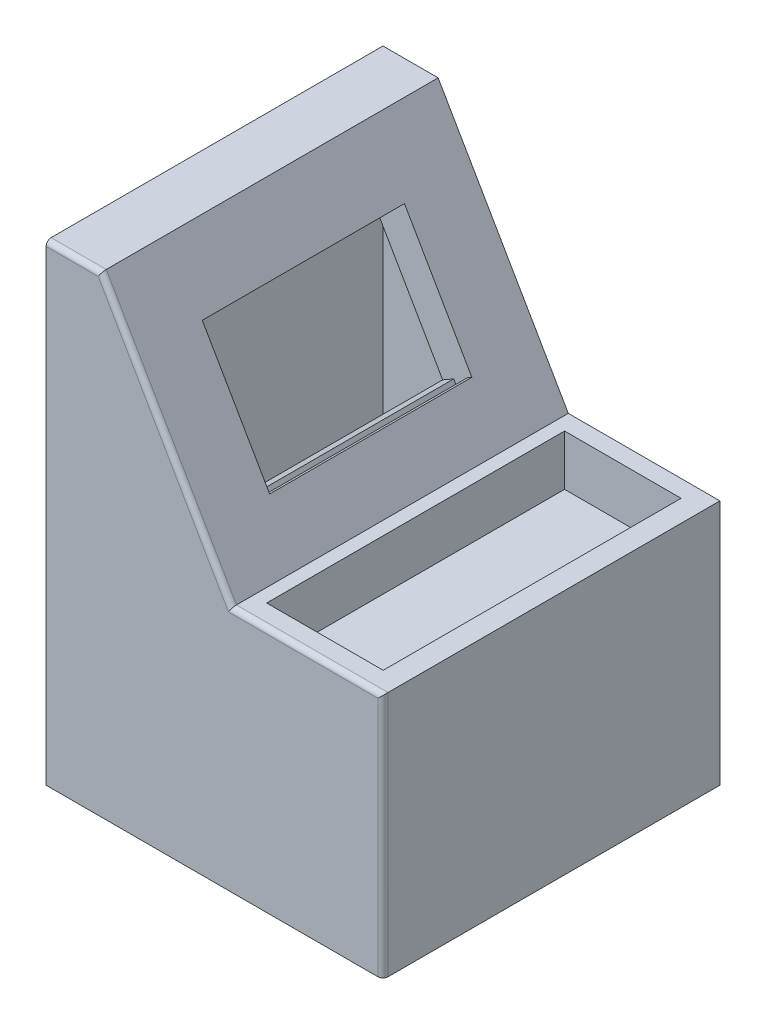
SolidWorks part; units mm, degrees
ref_plane "Front Plane" through (0, 0, 0) normal (0, 0, 1) x (1, 0, 0)
ref_plane "Top Plane" through (0, 0, 0) normal (0, 1, 0) x (1, 0, 0)
ref_plane "Right Plane" through (0, 0, 0) normal (1, 0, 0) x (0, 0, -1)
sketch "Sketch1" plane through (0, 0, 0) normal (0, 0, 1) x (1, 0, 0)
  line L0 (0, 203.2) -> (0, 711.2)
  line L1 (0, 0) -> (508, 0)
  line L2 (0, 0) -> (0, 203.2)
  line L3 (0, 203.2) -> (508, 203.2)
  line L4 (508, 0) -> (508, 203.2)
  line L5 (0, 711.2) -> (83.1288, 711.2)
  line L6 (83.1288, 711.2) -> (279.4, 371.2483)
  line L7 (279.4, 371.2483) -> (508, 371.2483)
  line L8 (508, 371.2483) -> (508, 203.2)
  dimension "D1" = 508
  dimension "D2" = 508
  dimension "D3" = 203.2
  dimension "D4" = 120
  dimension "D5" = 392.5424
  dimension "D6" = 228.6
extrude "Boss-Extrude1" add sketch "Sketch1" along normal blind 508 contours L8 L7 L6 L5 L0 L3 | L2 L1 L4 L3 region at (189.225, 380.8468, 0)
sketch "Sketch2" plane through (0, 371.2483, 0) normal (0, 1, 0) x (1, 0, 0)
  line L1 (299.6447, -25.9057) -> (475.366, -25.9057)
  line L2 (299.6447, -25.9057) -> (299.6447, -475.0665)
  line L3 (299.6447, -475.0665) -> (475.366, -475.0665)
  line L4 (475.366, -25.9057) -> (475.366, -475.0665)
extrude "Cut-Extrude1" cut sketch "Sketch2" against normal blind 76.2
sketch "Sketch3" plane through (370.3053, 213.7958, 0) normal (0.866, 0.5, 0) x (0, 0, -1)
  line L0 (0, 574.3529) -> (0, 181.8105) construction
  line L1 (-406.4, 472.7529) -> (-101.6, 472.7529)
  line L2 (-406.4, 472.7529) -> (-406.4, 269.5529)
  line L3 (-406.4, 269.5529) -> (-101.6, 269.5529)
  line L4 (-101.6, 472.7529) -> (-101.6, 269.5529)
  line L7 (-508, 574.3529) -> (0, 574.3529) construction
  dimension "D1" = 203.2
  dimension "D2" = 304.8
  dimension "D3" = 101.6
  dimension "D4" = 101.6
extrude "Cut-Extrude3" cut sketch "Sketch3" against normal blind 50.8
shell "Shell2" thickness 27.94 removed face at (140.7347, 509.8236, 254)
fillet "Fillet1" radius 7.62 4 edges at (41.5644, 711.2, 508) (181.2644, 541.2242, 508) (393.7, 371.2483, 508) (508, 185.6242, 508)
sketch "Sketch6" plane through (0, 0, 406.4) normal (0, 0, -1) x (-1, 0, 0)
  line L0 (-109.7118, 652.4423) -> (-240.0209, 424.215)
  line L1 (-275.0006, 363.6283) -> (-78.7294, 703.58) construction
  line L2 (-240.0209, 424.215) -> (-218.4495, 411.8986)
  line L3 (-218.4495, 411.8986) -> (-97.8271, 645.6566)
  line L4 (-97.8271, 645.6566) -> (-109.7118, 652.4423)
extrude "Cut-Extrude4" cut sketch "Sketch6" along normal up to surface (304.8 mm away) and the other way blind 97.536 up to face at (162.7318, 522.5236, 101.6)
ref_plane "Plane1" through (135.8523, 0, 0) normal (-1, 0, 0) x (0, 0, 1)
sketch "Sketch8" plane through (135.8523, 0, 0) normal (-1, 0, 0) x (0, 0, 1)
  line L4 (480.06, 267.1083) -> (480.06, 343.3083)
  line L5 (480.06, 343.3083) -> (27.94, 343.3083)
  line L6 (27.94, 343.3083) -> (27.94, 267.1083)
  line L7 (27.94, 267.1083) -> (480.06, 267.1083)
  line L8 (480.06, 267.1083) -> (480.06, 343.3083)
  line L9 (480.06, 343.3083) -> (27.94, 343.3083)
  line L10 (27.94, 343.3083) -> (27.94, 267.1083)
  line L11 (27.94, 267.1083) -> (480.06, 267.1083)
  dimension "D1" = 0
